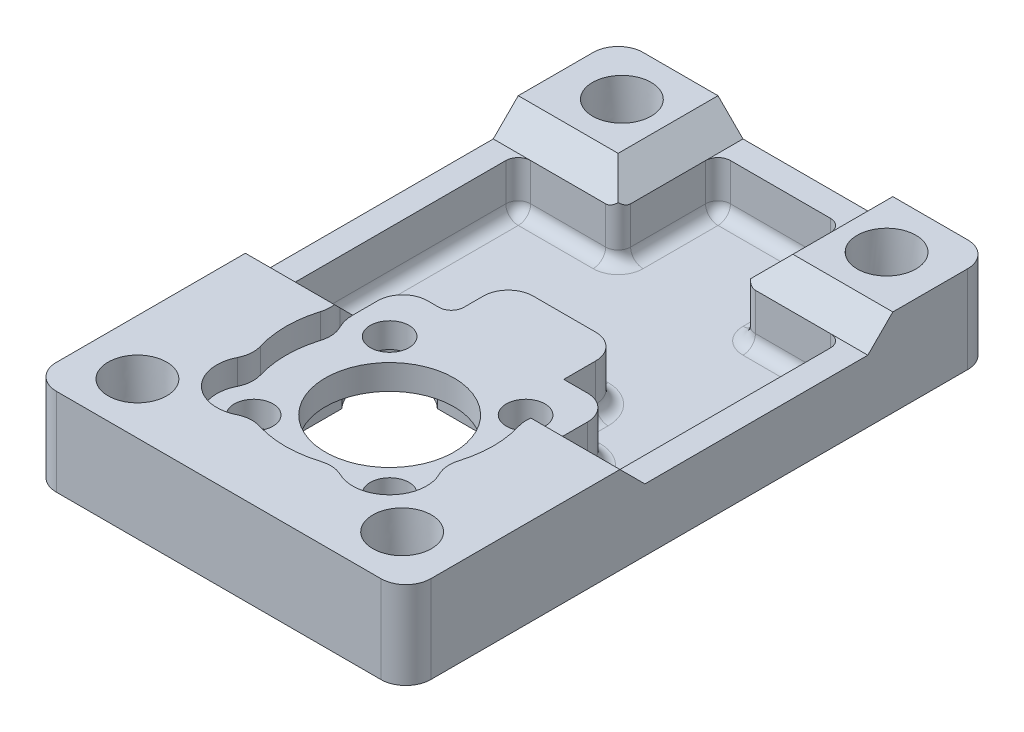
SolidWorks part; units mm, degrees
material "6061-T6 (SS)"
ref_plane "Front Plane" through (0, 0, 0) normal (0, 0, 1) x (1, 0, 0)
ref_plane "Top Plane" through (0, 0, 0) normal (0, 1, 0) x (1, 0, 0)
ref_plane "Right Plane" through (0, 0, 0) normal (1, 0, 0) x (0, 0, -1)
sketch "Sketch1" plane through (0, 0, 0) normal (0, 1, 0) x (1, 0, 0)
  line L1 (-19.05, -29.845) -> (19.05, -29.845)
  line L2 (-19.05, -29.845) -> (-19.05, 29.845)
  line L3 (-19.05, 29.845) -> (19.05, 29.845)
  line L4 (19.05, -29.845) -> (19.05, 29.845)
  line L5 (-19.05, -29.845) -> (19.05, 29.845) construction
  line L6 (-19.05, 29.845) -> (19.05, -29.845) construction
  point P0 (0, 0)
  dimension "D1" = 38.1
  dimension "D2" = 59.69
extrude "Boss-Extrude1" add sketch "Sketch1" along normal blind 8.89
sketch "Sketch2" plane through (0, 8.89, 0) normal (0, 1, 0) x (1, 0, 0)
  line L1 (-13.462, -24.638) -> (13.462, -24.638) construction
  line L2 (-13.462, -24.638) -> (-13.462, 24.638) construction
  line L3 (-13.462, 24.638) -> (13.462, 24.638) construction
  line L4 (13.462, -24.638) -> (13.462, 24.638) construction
  line L5 (-13.462, -24.638) -> (13.462, 24.638) construction
  line L6 (-13.462, 24.638) -> (13.462, -24.638) construction
  circle A0 centre (13.462, 24.638) radius 2.7813 construction
  circle A1 centre (-13.462, 24.638) radius 2.7813 construction
  circle A2 centre (-13.462, -24.638) radius 2.7813 construction
  circle A3 centre (13.462, -24.638) radius 2.7813 construction
  circle A4 centre (-13.462, 24.638) radius 2.9813
  point P0 (0, 0)
  dimension "D3" = 5.5626
  dimension "D1" = 49.276
  dimension "D2" = 26.924
  dimension "D4" = 0.2
ref_plane "Plane1" through (0, 4.318, 0) normal (0, 1, 0) x (1, 0, 0)
sketch "Sketch3" plane through (0, 4.318, 0) normal (0, 1, 0) x (1, 0, 0)
  circle A0 centre (-13.462, 24.638) radius 2.5781 construction
  circle A1 centre (-13.462, 24.638) radius 2.9813 construction
  circle A2 centre (-13.462, 24.638) radius 2.7781
  dimension "D1" = 5.1562
loft "Cut-Loft1" cut profiles "Sketch2", "Sketch3" connector at (-16.3963, 8.89, -25.1653) connector at (-16.2327, 4.318, -24.4357)
sketch "Sketch4" plane through (0, 4.318, 0) normal (0, 1, 0) x (1, 0, 0)
  circle A0 centre (-13.462, 24.638) radius 1.9685
  circle A1 centre (-13.462, 24.638) radius 2.7781 construction
  dimension "D1" = 3.937
extrude "Cut-Extrude1" cut sketch "Sketch4" against normal through all
pattern_linear "LPattern1" count 2 spacing 49.276 along (0, 0, 1) count 2 spacing 26.924 along (1, 0, 0) of "Cut-Extrude1", "Cut-Loft1"
sketch "Sketch5" plane through (0, 8.89, 0) normal (0, 1, 0) x (1, 0, 0)
  circle A0 centre (0, -12.446) radius 6.5405
  circle A1 centre (13.462, -24.638) radius 2.9813 construction
  dimension "D1" = 12.192
  dimension "D2" = 13.081
extrude "Cut-Extrude2" cut sketch "Sketch5" against normal offset from surface (7.62 mm away) 1.27 up to face at (-13.462, 0, 26.6065)
sketch "Sketch6" plane through (0, 8.89, 0) normal (0, 1, 0) x (1, 0, 0)
  line L0 (-10.293, -5.5312) -> (-10.293, 7.1688) construction
  line L1 (-6.9148, -19.3608) -> (6.9148, -19.3608) construction
  line L2 (-6.9148, -19.3608) -> (-6.9148, -5.5312) construction
  line L3 (-6.9148, -5.5312) -> (6.9148, -5.5312) construction
  line L4 (6.9148, -19.3608) -> (6.9148, -5.5312) construction
  line L5 (-6.9148, -19.3608) -> (6.9148, -5.5312) construction
  line L6 (-6.9148, -5.5312) -> (6.9148, -19.3608) construction
  line L7 (-10.293, 7.1688) -> (0, 7.1688) construction
  line L8 (0, 7.1688) -> (0, -5.5312) construction
  line L9 (-10.674, -5.5312) -> (-19.05, -5.5312)
  line L10 (-10.674, 7.5498) -> (10.674, 7.5498)
  line L11 (-19.05, 29.845) -> (-19.05, -29.845) construction
  line L12 (-19.05, -5.5312) -> (-19.05, 7.5498)
  line L13 (-19.05, 7.5498) -> (-10.674, 7.5498)
  line L14 (19.05, 7.5498) -> (10.674, 7.5498)
  line L15 (19.05, -5.5312) -> (19.05, 7.5498)
  line L16 (10.674, -5.5312) -> (19.05, -5.5312)
  circle A0 centre (0, -12.446) radius 10.16 construction
  arc A1 (-9.1616, -16.8381) -> (-4.3921, -21.6076) centre (-6.9148, -19.3608) ccw
  arc A2 (-9.1616, -8.0539) -> (-10.293, -5.5312) centre (-6.9148, -5.5312) cw construction
  arc A3 (-9.6214, -8.14) -> (-9.6214, -16.752) centre (0, -12.446) ccw
  arc A4 (-9.6214, -16.752) -> (-4.3542, -22.113) centre (-6.9148, -19.3608) ccw
  arc A5 (-4.3542, -22.113) -> (4.3542, -22.113) centre (0, -12.446) ccw
  arc A6 (-9.6214, -8.14) -> (-10.674, -5.5312) centre (-6.9148, -5.5312) cw
  arc A7 (9.6214, -8.14) -> (10.674, -5.5312) centre (6.9148, -5.5312) ccw
  arc A8 (9.6214, -8.14) -> (9.6214, -16.752) centre (0, -12.446) cw
  arc A9 (9.6214, -16.752) -> (4.3542, -22.113) centre (6.9148, -19.3608) cw
  point P25 (0, 7.5498)
  dimension "D1" = 20.32
  dimension "D3" = 3.3782
  dimension "D4" = 3.3782
  dimension "D2" = 19.558
  dimension "D5" = 12.7
  dimension "D6" = 0.381
  dimension "D7" = 0.381
  dimension "D8" = 0.4424
  dimension "D10" = 0.381
  dimension "D9" = 0.381
extrude "Cut-Extrude3" cut sketch "Sketch6" against normal offset from surface (2.54 mm away) 6.35 contours A9 A8 A7 L16 L14 L10 L13 L9 A6 A3 A4 A5 region at (0, 8.89, 3.9306) up to face at (-13.462, 0, 26.6065)
sketch "Sketch7" plane through (0, 0, 0) normal (0, -1, 0) x (1, 0, 0)
  circle A0 centre (-6.9148, 19.3608) radius 3.429
  circle A1 centre (6.9148, 19.3608) radius 3.429
  circle A2 centre (6.9148, 5.5312) radius 3.429
  circle A3 centre (-6.9148, 5.5312) radius 3.429
  dimension "D1" = 6.858
extrude "Cut-Extrude4" cut sketch "Sketch7" against normal blind 3.81
sketch "Sketch9" plane through (0, 3.81, 0) normal (0, -1, 0) x (1, 0, 0)
  circle A0 centre (6.9148, 5.5312) radius 1.9685
  circle A1 centre (-6.9148, 5.5312) radius 1.9685
  circle A2 centre (-6.9148, 19.3608) radius 1.9685
  circle A3 centre (6.9148, 19.3608) radius 1.9685
  dimension "D1" = 3.937
extrude "Cut-Extrude5" cut sketch "Sketch9" against normal through all
sketch "Sketch10" plane through (0, 0, 0) normal (0, -1, 0) x (1, 0, 0)
  line L1 (-9.3395, 21.7855) -> (9.3395, 21.7855)
  line L2 (-9.3395, 21.7855) -> (-9.3395, 3.1065)
  line L3 (-9.3395, 3.1065) -> (9.3395, 3.1065)
  line L4 (9.3395, 21.7855) -> (9.3395, 3.1065)
  circle A0 centre (6.9148, 19.3608) radius 3.429 construction
  circle A1 centre (-6.9148, 19.3608) radius 3.429 construction
  circle A2 centre (-6.9148, 5.5312) radius 3.429 construction
extrude "Cut-Extrude6" cut sketch "Sketch10" against normal up to surface (3.81 mm away) up to face at (-6.9148, 3.81, 17.3923)
chamfer "Chamfer1" distance 2.54 angle 45 2 edges at (-14.862, 8.89, 5.5312) (14.862, 8.89, 5.5312)
sketch "Sketch11" plane through (0, 8.89, 0) normal (0, 1, 0) x (1, 0, 0)
  line L0 (6.35, 29.845) -> (6.35, 17.145)
  line L1 (19.05, 29.845) -> (-19.05, 29.845) construction
  line L2 (6.35, 17.145) -> (19.05, 17.145)
  line L3 (19.05, 7.5498) -> (19.05, 29.845) construction
  line L4 (19.05, 17.145) -> (19.05, 7.5498)
  line L5 (19.05, 7.5498) -> (-19.05, 7.5498) construction
  line L6 (6.35, 29.845) -> (-6.35, 29.845)
  line L7 (0, 29.845) -> (0, 7.5498) construction
  line L8 (-19.05, 7.5498) -> (19.05, 7.5498)
  line L9 (-19.05, 17.145) -> (-19.05, 7.5498)
  line L10 (-6.35, 17.145) -> (-19.05, 17.145)
  line L11 (-6.35, 29.845) -> (-6.35, 17.145)
  dimension "D1" = 12.7
extrude "Cut-Extrude7" cut sketch "Sketch11" against normal up to surface (2.54 mm away) up to face at (-6.9148, 6.35, 3.5627)
chamfer "Chamfer2" distance 2.54 angle 45 4 edges at (12.7, 8.89, -17.145) (6.35, 8.89, -23.495) (-6.35, 8.89, -23.495) (-12.7, 8.89, -17.145)
sketch "Sketch12" plane through (0, 6.35, 0) normal (0, 1, 0) x (1, 0, 0)
  line L0 (-6.35, 27.305) -> (6.35, 27.305)
  line L1 (-6.35, 29.845) -> (-6.35, 17.145) construction
  line L2 (6.35, 17.145) -> (6.35, 29.845) construction
  line L3 (6.35, 27.305) -> (6.35, 17.145)
  line L4 (6.35, 17.145) -> (16.51, 17.145)
  line L5 (19.05, 17.145) -> (6.35, 17.145) construction
  line L6 (16.51, 17.145) -> (16.51, -5.5312)
  line L7 (-16.51, -5.5312) -> (-10.674, -5.5312)
  line L8 (-16.51, -5.5312) -> (-16.51, 17.145)
  line L9 (-6.35, 17.145) -> (-19.05, 17.145) construction
  line L10 (-16.51, 17.145) -> (-6.35, 17.145)
  line L11 (-6.35, 17.145) -> (-6.35, 27.305)
  line L12 (-10.674, -5.5312) -> (-19.05, -5.5312) construction
  line L13 (-10.674, -5.5312) -> (-10.674, -0.4512)
  line L14 (-10.674, -0.4512) -> (-5.715, -0.4512)
  line L15 (-5.715, -0.4512) -> (-5.715, 5.334)
  line L16 (-5.715, 5.334) -> (5.715, 5.334)
  line L17 (5.715, 5.334) -> (5.715, -0.4512)
  line L18 (5.715, -0.4512) -> (10.674, -0.4512)
  line L19 (10.674, -0.4512) -> (10.674, -5.5312)
  line L20 (10.674, -5.5312) -> (19.05, -5.5312) construction
  line L21 (10.674, -5.5312) -> (16.51, -5.5312)
  line L22 (0, 0) -> (0, 5.334) construction
  line L23 (19.05, 29.845) -> (-19.05, 29.845) construction
  line L24 (19.05, -5.5312) -> (19.05, 17.145) construction
  circle A0 centre (0, -12.446) radius 6.5405 construction
  dimension "D1" = 2.54
  dimension "D2" = 2.54
  dimension "D3" = 11.43
  dimension "D4" = 17.78
  dimension "D5" = 5.08
extrude "Cut-Extrude8" cut sketch "Sketch12" against normal offset from surface (5.08 mm away) 1.27 up to face at (0, 0, 12.446)
fillet "Fillet1" radius 2.54 4 edges at (5.715, 3.81, -5.334) (-5.715, 3.81, -5.334) (10.674, 3.81, 0.4512) (-10.674, 3.81, 0.4512)
fillet "Fillet2" radius 1.27 7 edges at (-16.51, 3.81, -17.145) (-6.35, 3.81, -17.145) (-6.35, 3.81, -27.305) (6.35, 3.81, -27.305) (6.35, 3.81, -17.145) (16.51, 3.81, -17.145) (-5.715, 3.81, 0.4512)
fillet "Fillet3" radius 1.27 27 edges at (-6.722, 1.27, -17.517) (-6.35, 1.27, -22.225) (-5.978, 1.27, -26.933) (0, 1.27, -27.305) (5.978, 1.27, -26.933) (6.35, 1.27, -22.225) (6.722, 1.27, -17.517) (11.43, 1.27, -17.145) (16.138, 1.27, -16.773) (16.51, 1.27, -5.1719) (13.592, 1.27, 5.5312) (10.674, 1.27, 4.2612) (9.93, 1.27, 1.1952) (6.9245, 1.27, 0.4512) (5.715, 1.27, -1.1714) (4.9711, 1.27, -4.5901) (0, 1.27, -5.334) (-4.9711, 1.27, -4.5901) (-5.715, 1.27, -1.8064) (-6.087, 1.27, 0.0792) (-7.5595, 1.27, 0.4512) (-9.93, 1.27, 1.1952) (-10.674, 1.27, 4.2612) (-13.592, 1.27, 5.5312) (-16.51, 1.27, -5.1719) (-16.138, 1.27, -16.773) (-11.43, 1.27, -17.145)
fillet "Fillet5" radius 2.54 4 edges at (-19.05, 4.445, -29.845) (-19.05, 4.445, 29.845) (19.05, 4.445, 29.845) (19.05, 4.445, -29.845)
fillet "Fillet6" radius 2.921 6 edges at (-9.6214, 7.62, 8.14) (-9.6214, 7.62, 16.752) (-4.3542, 7.62, 22.113) (4.3542, 7.62, 22.113) (9.6214, 7.62, 16.752) (9.6214, 7.62, 8.14)
equation "\"off1\"= 0.2mm"
equation "\"D4@Sketch2\"=\"off1\""
equation "\"D2@Sketch3\"=\"off1\""
equation "\"off2\"= 0.015in"
equation "\"D6@Sketch6\"=\"off2\""
equation "\"D10@Sketch6\"=\"off2\""
equation "\"D9@Sketch6\"=\"off2\""
equation "\"cb depth\"= 0.25in"
equation "\"D1@Cut-Extrude3\"=\"cb depth\""
equation "\"cham\"=0.1"
equation "\"D1@Chamfer1\"=\"cham\""
equation "\"D1@Chamfer2\"=\"cham\""
equation "\"wall\"=0.1"
equation "\"D1@Sketch12\"=\"wall\""
equation "\"D2@Sketch12\"=\"wall\""
